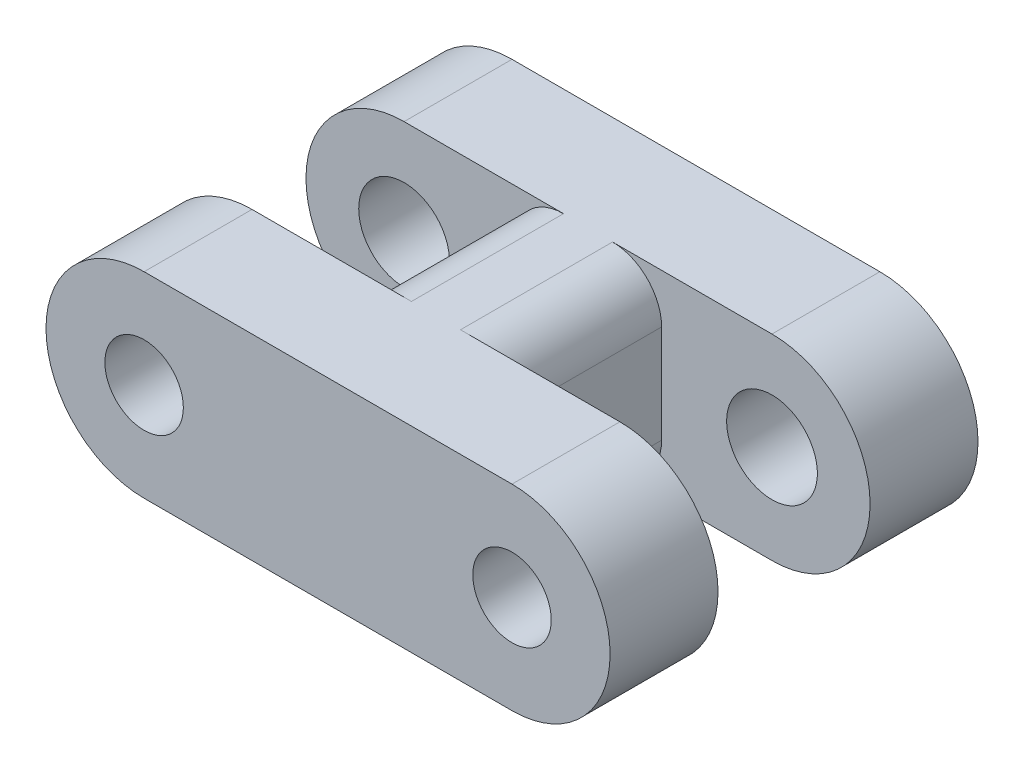
SolidWorks part; units mm, degrees
ref_plane "Front Plane" through (0, 0, 0) normal (0, 0, 1) x (1, 0, 0)
ref_plane "Top Plane" through (0, 0, 0) normal (0, 1, 0) x (1, 0, 0)
ref_plane "Right Plane" through (0, 0, 0) normal (1, 0, 0) x (0, 0, -1)
sketch "Sketch1" plane through (0, 0, 0) normal (0, 0, 1) x (1, 0, 0)
  line L0 (-15, 0) -> (0, 0) construction
  line L1 (-15, 4) -> (0, 4)
  line L2 (0, -4) -> (-15, -4)
  line L3 (-15, 0) -> (0, 0) construction
  arc A0 (0, -4) -> (0, 4) centre (0, 0) ccw
  arc A1 (-15, 4) -> (-15, -4) centre (-15, 0) ccw
  circle A2 centre (0, 0) radius 1.6
  circle A3 centre (-15, 0) radius 1.6
  dimension "D1" = 8
  dimension "D2" = 3.2
extrude "Boss-Extrude1" add sketch "Sketch1" along normal mid plane 15
sketch "Sketch2" plane through (0, 0, 0) normal (0, 1, 0) x (1, 0, 0)
  line L1 (5.5, 3.1) -> (-4.5, 3.1)
  line L2 (5.5, 3.1) -> (5.5, -3.1)
  line L3 (5.5, -3.1) -> (-4.5, -3.1)
  line L4 (-4.5, 3.1) -> (-4.5, -3.1)
  line L5 (-20.5, 3.1) -> (-10.5, 3.1)
  line L6 (-20.5, 3.1) -> (-20.5, -3.1)
  line L7 (-20.5, -3.1) -> (-10.5, -3.1)
  line L8 (-10.5, 3.1) -> (-10.5, -3.1)
  point P8 (-4.5, 0)
  point P10 (-10.5, 0)
  dimension "D1" = 6.2
  dimension "D2" = 4.5
  dimension "D3" = 4.5
  dimension "D4" = 10
extrude "Cut-Extrude1" cut sketch "Sketch2" against normal through all both and the other way through all
ref_axis "Axis1" through (0, 0, 7.5) along (0, 0, -1)
ref_axis "Axis2" through (-15, 0, 7.5) along (0, 0, -1)
hole_wizard "Hole1" positions "Sketch3" profile "Sketch4" legacy
sketch "Sketch3" plane through (0, 0, -7.5) normal (0, 0, -1) x (-1, 0, 0)
  point P0 (0, 0)
  point P3 (15, 0)
sketch "Sketch4" plane through (0, 0, -7.5) normal (1, 0, 0) x (0, 1, 0)
  line L0 (0, 0) -> (0, 4.4)
  line L1 (0, 4.4) -> (1.85, 4.4)
  line L2 (1.85, 4.4) -> (1.85, 0)
  line L3 (1.85, 0) -> (0, 0)
  line L4 (0, 110) -> (0, -10) construction
  dimension "Diameter" = 3.7
  dimension "Depth" = 4.4
fillet "Fillet1" radius 2 4 edges at (-4.5, -4, 0) (-10.5, -4, 0) (-4.5, 4, 0) (-10.5, 4, 0)
